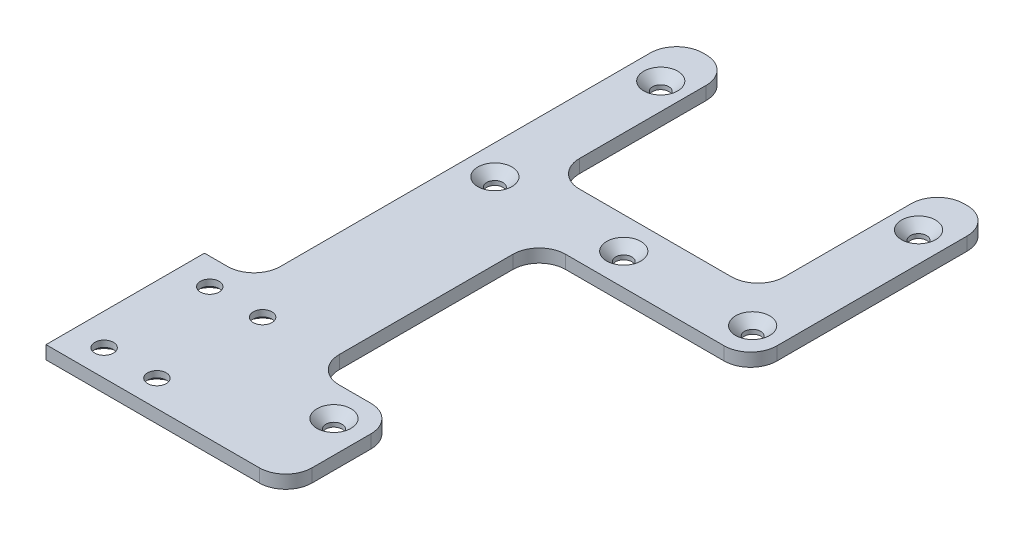
SolidWorks part; units mm, degrees
material "6061 Alloy"
ref_plane "Front Plane" through (0, 0, 0) normal (0, 0, 1) x (1, 0, 0)
ref_plane "Top Plane" through (0, 0, 0) normal (0, 1, 0) x (1, 0, 0)
ref_plane "Right Plane" through (0, 0, 0) normal (1, 0, 0) x (0, 0, -1)
sketch "Sketch1" plane through (0, 0, 0) normal (0, 1, 0) x (1, 0, 0)
  line L1 (-38.1, 88.9) -> (38.1, 88.9)
  line L2 (-38.1, 88.9) -> (-38.1, -88.9)
  line L3 (-38.1, -88.9) -> (38.1, -88.9)
  line L4 (38.1, 88.9) -> (38.1, -88.9)
  line L5 (-38.1, 88.9) -> (38.1, -88.9) construction
  line L6 (-38.1, -88.9) -> (38.1, 88.9) construction
  point P0 (0, 0)
  dimension "D1" = 76.2
  dimension "D2" = 177.8
extrude "Boss-Extrude1" add sketch "Sketch1" along normal blind 3.175
sketch "Sketch2" plane through (0, 3.175, 0) normal (0, 1, 0) x (1, 0, 0)
  line L0 (-30.988, 77.978) -> (-30.988, 38.1) construction
  line L1 (-30.988, 38.1) -> (30.988, 38.1) construction
  line L2 (30.988, 38.1) -> (30.988, 77.978) construction
  line L3 (0, 38.1) -> (0, -31.5722) construction
  line L4 (38.1, 88.9) -> (-38.1, 88.9) construction
  point P0 (30.988, 38.1)
  point P1 (0, 38.1)
  point P2 (-30.988, 38.1)
  point P3 (-30.988, 77.978)
  point P4 (30.988, 77.978)
  point P5 (0, -31.5722)
  dimension "D1" = 69.6722
  dimension "D2" = 61.976
  dimension "D3" = 39.878
  dimension "D4" = 50.8
hole_wizard "CSK for M3.5 Flat Head Machine Screw1" positions "Sketch4" profile "Sketch5" countersink size "M3.5" standard "Ansi Metric" end condition through all
sketch "Sketch4" plane through (0, 3.175, 0) normal (0, 1, 0) x (-1, 0, 0)
  line L0 (30.988, -38.1) -> (-30.988, -38.1) construction
  point P1 (30.988, -77.978)
  point P4 (-30.988, -77.978)
  point P7 (-30.988, -38.1)
  point P10 (0, -38.1)
  point P14 (30.988, -38.1)
  point P17 (0, 31.5722)
sketch "Sketch5" plane through (-30.988, 3.175, -77.978) normal (1, 0, 0) x (0, 0, 1)
  line L0 (0, 0) -> (0, 3.175)
  line L1 (0, 3.175) -> (1.95, 3.175)
  line L2 (1.95, 3.175) -> (1.95, 2.15)
  line L3 (1.95, 2.15) -> (4.1, 0)
  line L5 (4.1, 0) -> (0, 0)
  line L6 (-1.95, 2.15) -> (-4.1, 0) construction
  line L11 (0, -6.35) -> (0, 107.95) construction
  dimension "Thru Hole Dia." = 3.9
  dimension "Thru Hole Depth" = 3.175
  dimension "Near C'Sink Dia." = 8.2
  dimension "Near C'Sink Angle" = 90
sketch "Sketch7" plane through (0, 0, 0) normal (0, -1, 0) x (1, 0, 0)
  line L0 (-38.1, 50.8) -> (-50.0063, 50.8)
  line L1 (-38.1, -88.9) -> (-38.1, 88.9) construction
  line L2 (-50.0063, 50.8) -> (-50.0063, 12.7)
  line L3 (-50.0063, 12.7) -> (-38.1, 12.7)
  line L4 (-38.1, 12.7) -> (-38.1, 50.8)
  line L5 (-38.1, 88.9) -> (38.1, 88.9) construction
  dimension "D1" = 11.9062
  dimension "D2" = 38.1
  dimension "D3" = 38.1
extrude "Boss-Extrude2" add sketch "Sketch7" against normal up to surface (3.175 mm away) up to face at (-30.988, 3.175, -73.878)
hole_wizard "CSK for #8 Flat Head Machine Screw (100)1" positions "Sketch9" profile "Sketch8" countersink size "#8" standard "Ansi Inch" end condition through all
sketch "Sketch9" plane through (0, 0, 0) normal (0, -1, 0) x (1, 0, 0)
  line L1 (-42.3863, 44.45) -> (-29.6863, 44.45) construction
  line L2 (-42.3863, 44.45) -> (-42.3863, 19.05) construction
  line L3 (-42.3863, 19.05) -> (-29.6863, 19.05) construction
  line L4 (-29.6863, 44.45) -> (-29.6863, 19.05) construction
  line L5 (-50.0063, 50.8) -> (-50.0063, 12.7) construction
  line L7 (-50.0063, 31.75) -> (-42.3863, 31.75) construction
  point P0 (-29.6863, 44.45)
  point P1 (-42.3863, 19.05)
  point P3 (-42.3863, 44.45)
  point P5 (-29.6863, 19.05)
  dimension "D1" = 25.4
  dimension "D2" = 12.7
  dimension "D3" = 7.62
sketch "Sketch8" plane through (-29.6863, 0, 44.45) normal (1, 0, 0) x (0, 0, -1)
  line L0 (0, 0) -> (0, 3.175)
  line L1 (0, 3.175) -> (2.2479, 3.175)
  line L2 (2.2479, 3.175) -> (2.2479, 1.6518)
  line L3 (2.2479, 1.6518) -> (4.2164, 0)
  line L5 (4.2164, 0) -> (0, 0)
  line L6 (-2.2479, 1.6518) -> (-4.2164, 0) construction
  line L11 (0, -6.35) -> (0, 107.95) construction
  dimension "Thru Hole Dia." = 4.4958
  dimension "Thru Hole Depth" = 3.175
  dimension "Near C'Sink Dia." = 8.4328
  dimension "Near C'Sink Angle" = 100
sketch "Sketch10" plane through (0, 0, 0) normal (0, -1, 0) x (1, 0, 0)
  line L0 (38.1, 88.9) -> (38.1, -88.9) construction
  line L1 (-38.1, 88.9) -> (38.1, 88.9)
  line L2 (-38.1, 88.9) -> (-38.1, 50.8)
  line L3 (-38.1, 50.8) -> (38.1, 50.8)
  line L4 (38.1, 88.9) -> (38.1, 50.8)
  line L5 (-38.1, 50.8) -> (-50.0063, 50.8) construction
extrude "Cut-Extrude2" cut sketch "Sketch10" against normal through all
sketch "Sketch11" plane through (0, 0, 0) normal (0, -1, 0) x (1, 0, 0)
  line L0 (-30.988, -77.978) -> (-30.988, -38.1) construction
  line L1 (-24.638, -45.72) -> (24.638, -45.72)
  line L2 (-24.638, -45.72) -> (-24.638, -88.9)
  line L3 (-24.638, -88.9) -> (24.638, -88.9)
  line L4 (24.638, -45.72) -> (24.638, -88.9)
  line L5 (-24.638, -45.72) -> (24.638, -88.9) construction
  line L6 (-24.638, -88.9) -> (24.638, -45.72) construction
  line L7 (-30.988, -38.1) -> (30.988, -38.1) construction
  line L8 (38.1, -88.9) -> (-38.1, -88.9) construction
  point P0 (0, -67.31)
  dimension "D1" = 6.35
  dimension "D2" = 7.62
extrude "Cut-Extrude3" cut sketch "Sketch11" against normal through all
sketch "Sketch12" plane through (0, 0, 0) normal (0, -1, 0) x (1, 0, 0)
  line L0 (7.62, 50.8) -> (7.62, 23.9522)
  line L1 (38.1, 50.8) -> (-50.0063, 50.8) construction
  line L2 (7.62, 23.9522) -> (-12.7, 23.9522)
  line L3 (-12.7, 23.9522) -> (-12.7, -30.48)
  line L4 (-12.7, -30.48) -> (38.1, -30.48)
  line L5 (38.1, 50.8) -> (38.1, -88.9) construction
  line L6 (38.1, -30.48) -> (38.1, 50.8)
  line L7 (38.1, 50.8) -> (7.62, 50.8)
  line L8 (0, -38.1) -> (0, 31.5722) construction
  line L9 (-38.1, -88.9) -> (-38.1, 12.7) construction
  line L10 (-30.988, -38.1) -> (30.988, -38.1) construction
  dimension "D1" = 7.62
  dimension "D2" = 7.62
  dimension "D3" = 25.4
  dimension "D4" = 7.62
extrude "Cut-Extrude4" cut sketch "Sketch12" against normal through all
fillet "Fillet2" radius 6.35 7 edges at (7.62, 1.5875, 23.9522) (38.1, 1.5875, -30.48) (-12.7, 1.5875, -30.48) (24.638, 1.5875, -45.72) (-24.638, 1.5875, -45.72) (-12.7, 1.5875, 23.9522)
fillet "Fillet3" radius 6.35 5 edges at (-38.1, 1.5875, -88.9) (-24.638, 1.5875, -88.9) (24.638, 1.5875, -88.9) (38.1, 1.5875, -88.9) (7.62, 1.5875, 50.8)
sketch "Sketch13" plane through (0, 0, 0) normal (0, -1, 0) x (1, 0, 0)
  line L1 (-50.0063, 50.8) -> (-20.2975, 50.8)
  line L2 (-50.0063, 50.8) -> (-50.0063, 12.7945)
  line L3 (-50.0063, 12.7945) -> (-20.2975, 12.7945)
  line L4 (-20.2975, 50.8) -> (-20.2975, 12.7945)
extrude "Cut-Extrude5" [suppressed] cut sketch "Sketch13" against normal blind 0.0003
